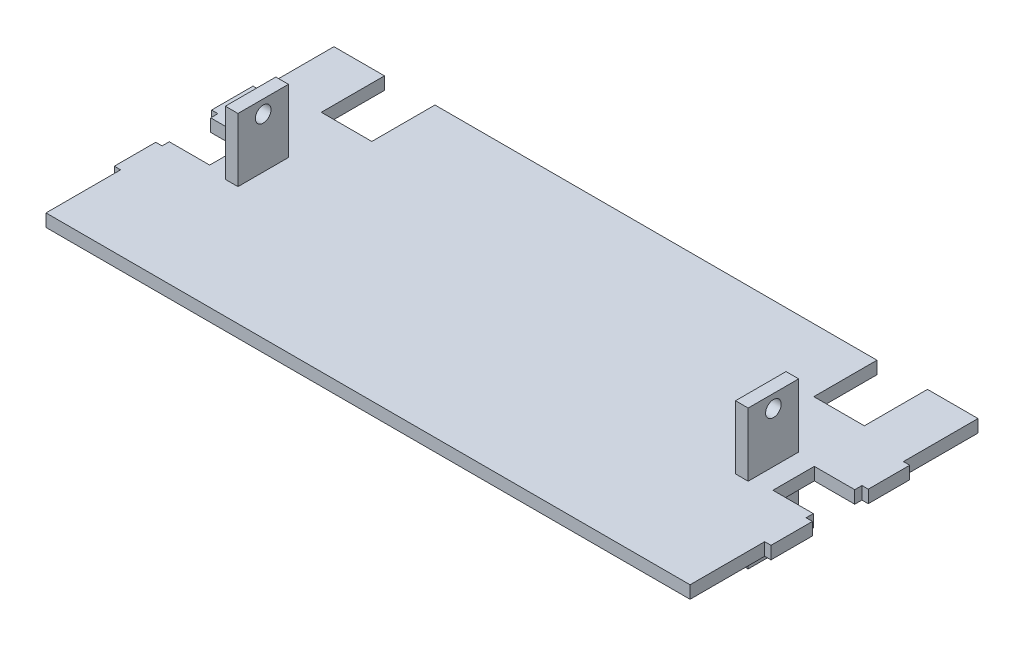
SolidWorks part; units mm, degrees
ref_plane "Front Plane" through (0, 0, 0) normal (0, 0, 1) x (1, 0, 0)
ref_plane "Top Plane" through (0, 0, 0) normal (0, 1, 0) x (1, 0, 0)
ref_plane "Right Plane" through (0, 0, 0) normal (1, 0, 0) x (0, 0, -1)
sketch "Sketch1" plane through (0, 0, 0) normal (0, 1, 0) x (1, 0, 0)
  line L0 (0, 72.39) -> (0, -72.39) construction
  line L1 (161.925, -72.39) -> (-161.925, -72.39)
  line L2 (161.925, -72.39) -> (161.925, -34.8747)
  line L3 (161.925, 72.39) -> (136.525, 72.39)
  line L4 (-161.925, -72.39) -> (-161.925, -34.8747)
  line L5 (161.925, -72.39) -> (-161.925, 72.39) construction
  line L6 (161.925, 72.39) -> (-161.925, -72.39) construction
  line L7 (161.925, 10.414) -> (141.605, 10.414)
  line L9 (161.925, -10.414) -> (141.605, -10.414)
  line L10 (141.605, 10.414) -> (141.605, -10.414)
  line L11 (-136.525, 72.39) -> (-161.925, 72.39)
  line L13 (-161.925, -10.414) -> (-141.605, -10.414)
  line L14 (-141.605, 10.414) -> (-141.605, -10.414)
  line L15 (-161.925, 10.414) -> (-141.605, 10.414)
  line L17 (-127, 0) -> (127, 0) construction
  line L18 (-161.925, 14.0467) -> (-165.1, 14.0467)
  line L20 (-161.925, 34.8747) -> (-165.1, 34.8747)
  line L21 (-165.1, 14.0467) -> (-165.1, 34.8747)
  line L22 (-161.925, -34.8747) -> (-165.1, -34.8747)
  line L23 (-165.1, -14.0467) -> (-165.1, -34.8747)
  line L24 (-161.925, -14.0467) -> (-165.1, -14.0467)
  line L27 (161.925, -14.0467) -> (165.1, -14.0467)
  line L28 (165.1, -14.0467) -> (165.1, -34.8747)
  line L29 (161.925, -34.8747) -> (165.1, -34.8747)
  line L30 (161.925, 34.8747) -> (165.1, 34.8747)
  line L31 (165.1, 14.0467) -> (165.1, 34.8747)
  line L32 (161.925, 14.0467) -> (165.1, 14.0467)
  line L34 (-161.925, 34.8747) -> (-161.925, 72.39)
  line L35 (-161.925, -14.0467) -> (-161.925, -10.414)
  line L36 (161.925, 34.8747) -> (161.925, 72.39)
  line L37 (161.925, -14.0467) -> (161.925, -10.414)
  line L38 (-161.925, 10.414) -> (-161.925, 14.0467)
  line L39 (161.925, 10.414) -> (161.925, 14.0467)
  line L40 (-136.525, 72.39) -> (-136.525, 40.64)
  line L41 (-136.525, 40.64) -> (-111.125, 40.64)
  line L42 (-111.125, 72.39) -> (-111.125, 40.64)
  line L44 (111.125, 72.39) -> (111.125, 40.64)
  line L45 (111.125, 40.64) -> (136.525, 40.64)
  line L46 (136.525, 72.39) -> (136.525, 40.64)
  line L47 (111.125, 72.39) -> (-111.125, 72.39)
  point P0 (0, 0)
  point P6 (127, 0)
  dimension "D1" = 323.85
  dimension "D2" = 144.78
  dimension "D3" = 20.828
  dimension "D5" = 3.175
  dimension "D6" = 20.828
  dimension "D4" = 20.32
  dimension "D7" = 31.75
  dimension "D8" = 25.4
  dimension "D9" = 25.4
  dimension "D10" = 31.75
  dimension "D12" = 25.4
  dimension "D11" = 25.4
extrude "Boss-Extrude1" add sketch "Sketch1" along normal mid plane 6.35
sketch "Sketch2" plane through (0, 0, 0) normal (0, 1, 0) x (1, 0, 0)
  line L0 (-141.605, 10.414) -> (-141.605, -10.414) construction
  line L1 (125.095, -12.7) -> (131.445, -12.7)
  line L2 (125.095, -12.7) -> (125.095, 12.7)
  line L3 (125.095, 12.7) -> (131.445, 12.7)
  line L4 (131.445, -12.7) -> (131.445, 12.7)
  line L5 (125.095, -12.7) -> (131.445, 12.7) construction
  line L6 (125.095, 12.7) -> (131.445, -12.7) construction
  line L9 (-125.095, -12.7) -> (-125.095, 12.7)
  line L10 (-125.095, 12.7) -> (-131.445, 12.7)
  line L11 (-131.445, -12.7) -> (-131.445, 12.7)
  line L12 (-125.095, -12.7) -> (-131.445, -12.7)
  line L13 (141.605, -10.414) -> (141.605, 10.414) construction
  point P0 (128.27, 0)
  point P10 (141.605, 0)
  dimension "D1" = 10.16
  dimension "D2" = 10.16
  dimension "D3" = 25.4
  dimension "D4" = 25.4
  dimension "D5" = 6.35
  dimension "D6" = 6.35
  dimension "D7" = 6.35
extrude "Boss-Extrude2" add sketch "Sketch2" along normal mid plane 70.104
sketch "Sketch3" plane through (-131.445, 0, 0) normal (-1, 0, 0) x (0, 0, 1)
  circle A0 centre (0, 28.4406) radius 3.937
  circle A1 centre (0, -28.4406) radius 3.937
  dimension "D1" = 7.874
  dimension "D2" = 7.874
extrude "Cut-Extrude1" cut sketch "Sketch3" against normal through all both and the other way through all
equation "\"Avionics_Board_Length\"= 12.75"
equation "\"width\"= 5.7"
equation "\"height\"= 0.25"
equation "\"D1@Sketch1\"=\"Avionics_Board_Length\""
equation "\"D2@Sketch1\"=\"width\""
equation "\"eyebolt width\"= 0.82"
equation "\"eyebolt length\"= 0.8"
equation "\"D3@Sketch1\"=\"eyebolt width\""
equation "\"D4@Sketch1\"=\"eyebolt length\""
equation "\"lead screw holder height\"= 2.76"
equation "\"lead screw diameter\"= 0.31"
equation "\"D1@Sketch3\"=\"lead screw diameter\""
equation "\"distance from holders to board\"=0.4"
equation "\"D2@Sketch3\"=\"lead screw diameter\""
